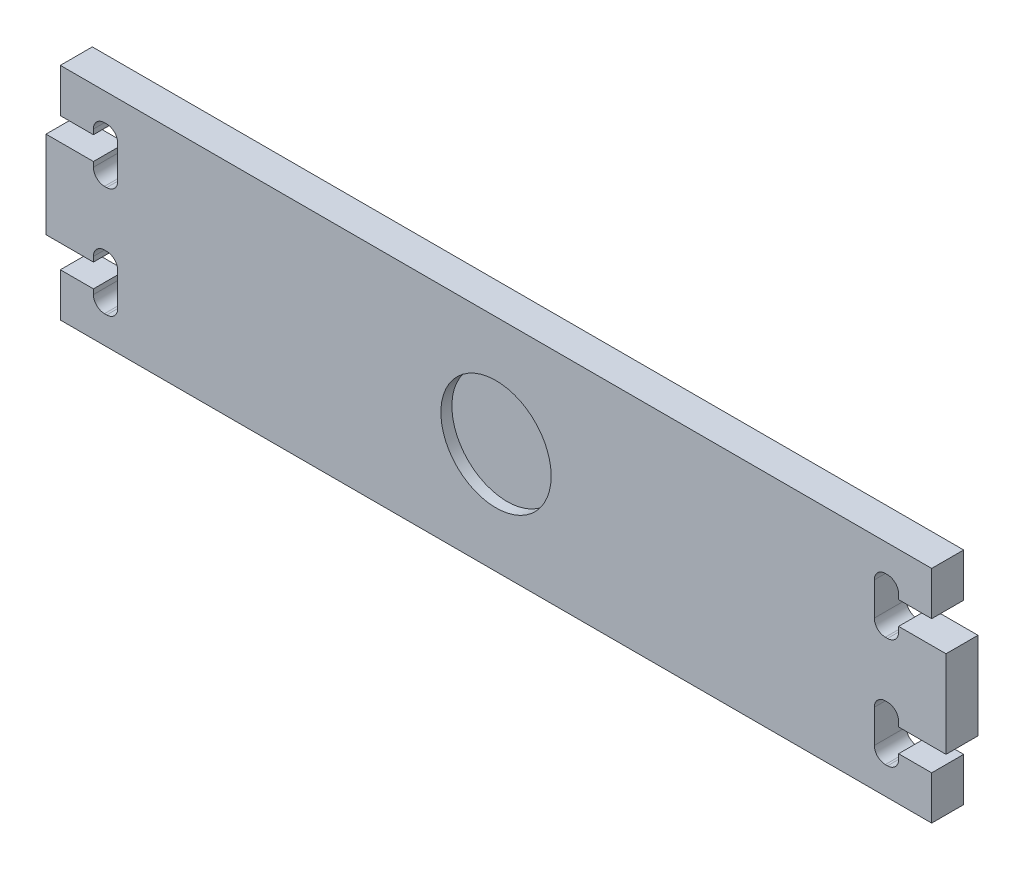
SolidWorks part; units mm, degrees
ref_plane "Front Plane" through (0, 0, 0) normal (0, 0, 1) x (1, 0, 0)
ref_plane "Top Plane" through (0, 0, 0) normal (0, 1, 0) x (1, 0, 0)
ref_plane "Right Plane" through (0, 0, 0) normal (1, 0, 0) x (0, 0, -1)
sketch "Sketch1" plane through (0, 0, 0) normal (0, 0, 1) x (1, 0, 0)
  line L0 (-39.5, 0) -> (39.5, 0) construction
  line L1 (-39.5, 10) -> (39.5, 10)
  line L2 (-39.5, 10) -> (-39.5, -10)
  line L3 (-39.5, -10) -> (39.5, -10)
  line L4 (39.5, 10) -> (39.5, -10)
  line L5 (-39.5, 10) -> (39.5, -10) construction
  line L6 (-39.5, -10) -> (39.5, 10) construction
  line L7 (0, 10) -> (0, -10) construction
  line L9 (-40.8, -3.95) -> (-39.5, -3.95)
  line L10 (-40.8, -3.95) -> (-40.8, 3.95)
  line L11 (-40.8, 3.95) -> (-39.5, 3.95)
  line L12 (-39.5, -3.95) -> (-39.5, 3.95)
  line L13 (-40.8, -3.95) -> (-39.5, 3.95) construction
  line L14 (-40.8, 3.95) -> (-39.5, -3.95) construction
  line L16 (40.8, 3.95) -> (39.5, 3.95)
  line L17 (40.8, -3.95) -> (40.8, 3.95)
  line L18 (40.8, -3.95) -> (39.5, -3.95)
  line L19 (-39.5, 5) -> (39.5, 5) construction
  line L20 (-35.4, 7.5) -> (-35.4, 2.5) construction
  line L21 (-36.5, 3.95) -> (-39.5, 3.95)
  line L22 (-36.5, 3.95) -> (-36.5, 6.05)
  line L23 (-36.5, 6.05) -> (-39.5, 6.05)
  line L24 (-39.5, 3.95) -> (-39.5, 6.05)
  line L25 (-36.5, 3.95) -> (-39.5, 6.05) construction
  line L26 (-36.5, 6.05) -> (-39.5, 3.95) construction
  line L27 (-34.3, 7.5) -> (-36.5, 7.5)
  line L28 (-34.3, 7.5) -> (-34.3, 2.5)
  line L29 (-34.3, 2.5) -> (-36.5, 2.5)
  line L30 (-36.5, 7.5) -> (-36.5, 2.5)
  line L31 (-34.3, 7.5) -> (-36.5, 2.5) construction
  line L32 (-34.3, 2.5) -> (-36.5, 7.5) construction
  line L33 (-34.3, -7.5) -> (-36.5, -7.5)
  line L34 (-34.3, -7.5) -> (-34.3, -2.5)
  line L35 (-34.3, -2.5) -> (-36.5, -2.5)
  line L36 (-36.5, -7.5) -> (-36.5, -2.5)
  line L37 (-36.5, -3.95) -> (-39.5, -3.95)
  line L38 (-36.5, -6.05) -> (-39.5, -6.05)
  line L39 (36.5, 3.95) -> (39.5, 3.95)
  line L40 (36.5, 6.05) -> (39.5, 6.05)
  line L41 (36.5, 7.5) -> (36.5, 2.5)
  line L42 (34.3, 7.5) -> (36.5, 7.5)
  line L43 (34.3, 7.5) -> (34.3, 2.5)
  line L44 (34.3, 2.5) -> (36.5, 2.5)
  line L45 (34.3, -2.5) -> (36.5, -2.5)
  line L46 (34.3, -7.5) -> (34.3, -2.5)
  line L47 (34.3, -7.5) -> (36.5, -7.5)
  line L48 (36.5, -7.5) -> (36.5, -2.5)
  line L49 (36.5, -6.05) -> (39.5, -6.05)
  line L50 (36.5, -3.95) -> (39.5, -3.95)
  point P0 (0, 0)
  point P10 (-40.15, 0)
  point P15 (-38, 5)
  point P35 (-35.4, 5)
  dimension "D1" = 79
  dimension "D2" = 20
  dimension "D4" = 1.3
  dimension "D7" = 5
  dimension "D8" = 2.1
  dimension "D9" = 3
  dimension "D10" = 2.2
  dimension "D11" = 5
extrude "Base shape" add sketch "Sketch1" along normal blind 2.9 contours L4 L1 L2 L3 | L9 L2 L11 L10 | L16 L4 L18 L17 region at (0, 0, 0) region at (-40.15, 0, 0) region at (40.15, 0, 0)
sketch "Sketch2" plane through (0, 0, 2.9) normal (0, 0, 1) x (1, 0, 0)
  circle A0 centre (0, 0) radius 5
  dimension "D1" = 10
extrude "Forward cut (temp)" cut sketch "Sketch2" against normal blind 1
fillet "Fillet1" radius 1 16 edges at (36.5, -7.5, 1.45) (36.5, 2.5, 1.45) (34.3, 2.5, 1.45) (34.3, -7.5, 1.45) (36.5, -2.5, 1.45) (36.5, 7.5, 1.45) (34.3, -2.5, 1.45) (34.3, 7.5, 1.45) (-36.5, -2.5, 1.45) (-34.3, -2.5, 1.45) (-34.3, -7.5, 1.45) (-36.5, -7.5, 1.45) (-36.5, 2.5, 1.45) (-34.3, 2.5, 1.45) (-34.3, 7.5, 1.45) (-36.5, 7.5, 1.45)
sketch "Sketch3" plane through (-40.8, 0, 0) normal (-1, 0, 0) x (0, 0, 1)
  line L0 (0, 6.05) -> (2.9, 3.95) construction
  line L1 (0, 6.05) -> (2.9, 6.05)
  line L2 (0, 6.05) -> (0, 3.95)
  line L3 (0, 3.95) -> (2.9, 3.95)
  line L4 (2.9, 6.05) -> (2.9, 3.95)
  line L5 (0, -3.95) -> (2.9, -6.05) construction
  line L6 (0, -3.95) -> (2.9, -3.95)
  line L7 (0, -3.95) -> (0, -6.05)
  line L8 (0, -6.05) -> (2.9, -6.05)
  line L9 (2.9, -3.95) -> (2.9, -6.05)
  point P6 (1.45, 5)
  point P13 (1.45, -5)
ref_axis "Tap axis top" through (-53.7846, 5, 1.45) along (1, 0, 0)
ref_axis "Tap axis bottom" through (-54.2844, -5, 1.45) along (1, 0, 0)
